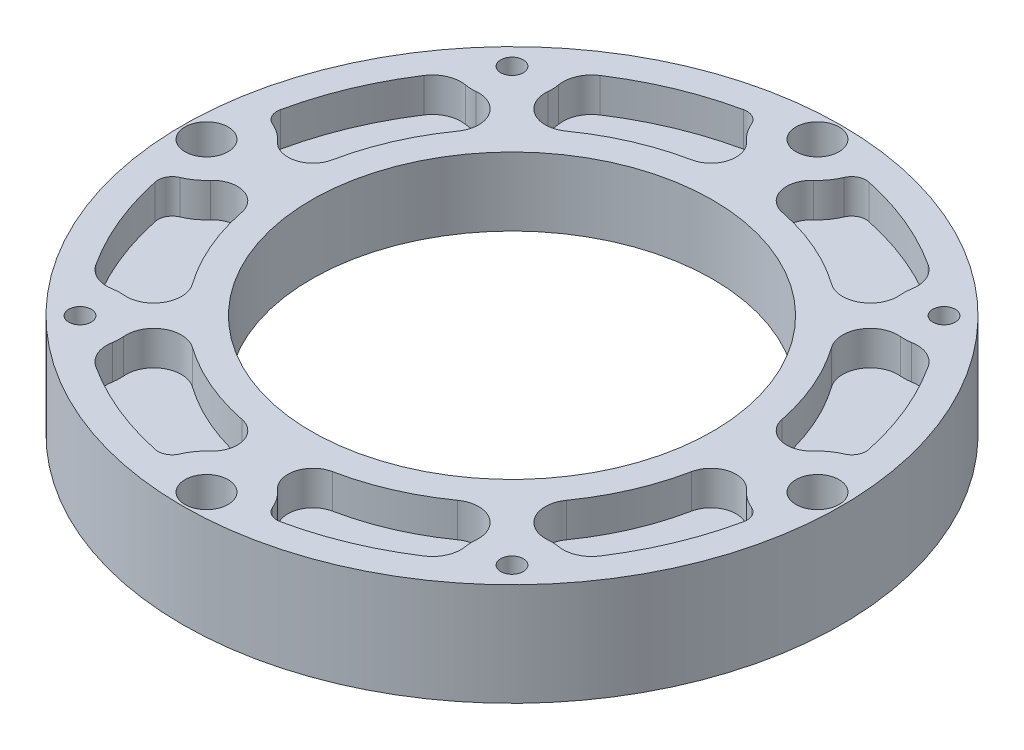
SolidWorks part; units mm, degrees
ref_plane "Front Plane" through (0, 0, 0) normal (0, 0, 1) x (1, 0, 0)
ref_plane "Top Plane" through (0, 0, 0) normal (0, 1, 0) x (1, 0, 0)
ref_plane "Right Plane" through (0, 0, 0) normal (1, 0, 0) x (0, 0, -1)
sketch "Sketch1" plane through (0, 0, 0) normal (0, 1, 0) x (1, 0, 0)
  line L0 (0, 0) -> (42.5, 0) construction
  circle A0 centre (0, 0) radius 45.85
  circle A1 centre (0, 0) radius 27.9
  circle A2 centre (42.5, 0) radius 1.5635
  circle A3 centre (30.052, -30.052) radius 1.5635
  circle A4 centre (0, -42.5) radius 1.5635
  circle A5 centre (0, 0) radius 40.5
  circle A6 centre (-30.052, -30.052) radius 1.5635
  circle A7 centre (-42.5, 0) radius 1.5635
  circle A8 centre (-30.052, 30.052) radius 1.5635
  circle A9 centre (0, 42.5) radius 1.5635
  circle A10 centre (30.052, 30.052) radius 1.5635
  point P13 (0, 0)
  dimension "D1" = 91.7
  dimension "D2" = 55.8
  dimension "D4" = 3.127
  dimension "D6" = 81
  dimension "D3" = 42.5
  dimension "D5" = 8
extrude "Boss-Extrude1" add sketch "Sketch1" against normal blind 4.7625 contours A0 A5 A2 A4 A3 region at (-44.5532, 0, 0)
extrude "Boss-Extrude2" add sketch "Sketch1<4>" along normal blind 4.7625 contours A1 A5 | A0 A5 A2 A4 A3 region at (-44.5532, 0, 0) region at (-39.3545, 0, 0)
sketch "Sketch1<4>" plane through (0, 0, 0) normal (0, 1, 0) x (1, 0, 0) same geometry as "Sketch1"
sketch "Sketch4" plane through (0, 4.7625, 0) normal (0, 1, 0) x (1, 0, 0)
  line L0 (28.4932, -27.352) -> (26.9343, -30.052)
  line L7 (30.052, 33.1697) -> (27.352, 31.6109)
  line L8 (27.352, 31.6109) -> (27.352, 28.4932)
  line L9 (27.352, 28.4932) -> (30.052, 26.9343)
  line L10 (30.052, 26.9343) -> (32.752, 28.4932)
  line L11 (32.752, 28.4932) -> (32.752, 31.6109)
  line L12 (32.752, 31.6109) -> (30.052, 33.1697)
  line L13 (31.6109, -27.352) -> (28.4932, -27.352)
  line L14 (33.1697, -30.052) -> (31.6109, -27.352)
  line L15 (31.6109, -32.752) -> (33.1697, -30.052)
  line L16 (28.4932, -32.752) -> (31.6109, -32.752)
  line L17 (26.9343, -30.052) -> (28.4932, -32.752)
  line L18 (-27.352, -28.4932) -> (-30.052, -26.9343)
  line L19 (-27.352, -31.6109) -> (-27.352, -28.4932)
  line L20 (-30.052, -33.1697) -> (-27.352, -31.6109)
  line L21 (-32.752, -31.6109) -> (-30.052, -33.1697)
  line L22 (-32.752, -28.4932) -> (-32.752, -31.6109)
  line L23 (-30.052, -26.9343) -> (-32.752, -28.4932)
  line L24 (-28.4932, 27.352) -> (-26.9343, 30.052)
  line L25 (-31.6109, 27.352) -> (-28.4932, 27.352)
  line L26 (-33.1697, 30.052) -> (-31.6109, 27.352)
  line L27 (-31.6109, 32.752) -> (-33.1697, 30.052)
  line L28 (-28.4932, 32.752) -> (-31.6109, 32.752)
  line L29 (-26.9343, 30.052) -> (-28.4932, 32.752)
  circle A0 centre (30.052, 30.052) radius 2.7 construction
  point P1 (31.402, 32.3903)
  point P32 (0, 0)
  dimension "D1" = 5.4
  dimension "D2" = 4
extrude "Cut-Extrude2" cut sketch "Sketch4" against normal blind 4.7625
sketch "Sketch3" plane through (0, 4.7625, 0) normal (0, 1, 0) x (1, 0, 0)
  circle A6 centre (0, -42.5) radius 1.5635 construction
  circle A7 centre (42.5, 0) radius 1.5635 construction
  circle A8 centre (0, 42.5) radius 1.5635 construction
  circle A9 centre (-42.5, 0) radius 1.5635 construction
  circle A10 centre (0, 0) radius 27.9 construction
  circle A11 centre (0, 0) radius 45.85 construction
  circle A12 centre (0, -42.5) radius 1.5635
  circle A13 centre (42.5, 0) radius 1.5635
  circle A14 centre (0, 42.5) radius 1.5635
  circle A15 centre (-42.5, 0) radius 1.5635
  circle A16 centre (0, 0) radius 27.9
  circle A17 centre (0, 0) radius 45.85
  circle A18 centre (0, 42.5) radius 3
  circle A19 centre (42.5, 0) radius 3
  circle A20 centre (0, -42.5) radius 3
  circle A21 centre (-42.5, 0) radius 3
  circle A22 centre (-30.052, 30.052) radius 1.565
  circle A23 centre (30.052, 30.052) radius 1.565
  circle A24 centre (30.052, -30.052) radius 1.565
  circle A25 centre (-30.052, -30.052) radius 1.565
  circle M1 centre (0, 0) radius 27.9
  circle M6 centre (0, 0) radius 45.85
  line M21 (-33.1697, 30.052) -> (-31.6109, 32.752)
  line M22 (-31.6109, 32.752) -> (-28.4932, 32.752)
  line M23 (-28.4932, 32.752) -> (-26.9343, 30.052)
  line M24 (-26.9343, 30.052) -> (-28.4932, 27.352)
  line M25 (-28.4932, 27.352) -> (-31.6109, 27.352)
  line M26 (-31.6109, 27.352) -> (-33.1697, 30.052)
  line M27 (-30.052, -33.1697) -> (-32.752, -31.6109)
  line M28 (-32.752, -31.6109) -> (-32.752, -28.4932)
  line M29 (-32.752, -28.4932) -> (-30.052, -26.9343)
  line M30 (-30.052, -26.9343) -> (-27.352, -28.4932)
  line M31 (-27.352, -28.4932) -> (-27.352, -31.6109)
  line M32 (-27.352, -31.6109) -> (-30.052, -33.1697)
  line M33 (33.1697, -30.052) -> (31.6109, -32.752)
  line M34 (31.6109, -32.752) -> (28.4932, -32.752)
  line M35 (28.4932, -32.752) -> (26.9343, -30.052)
  line M36 (26.9343, -30.052) -> (28.4932, -27.352)
  line M37 (28.4932, -27.352) -> (31.6109, -27.352)
  line M38 (31.6109, -27.352) -> (33.1697, -30.052)
  line M39 (30.052, 33.1697) -> (32.752, 31.6109)
  line M40 (32.752, 31.6109) -> (32.752, 28.4932)
  line M41 (32.752, 28.4932) -> (30.052, 26.9343)
  line M42 (30.052, 26.9343) -> (27.352, 28.4932)
  line M43 (27.352, 28.4932) -> (27.352, 31.6109)
  line M44 (27.352, 31.6109) -> (30.052, 33.1697)
  dimension "D1" = 6
  dimension "D2" = 3.13
extrude "Boss-Extrude3" add sketch "Sketch3" along normal blind 4.7625 contours A21 A20 A19 A18 M6 M1 M44 M39 M40 M41 M42 M43 M38 M33 M34 M35 M36 M37 M32 M27 M28 M29 M30 M31 M26 M21 M22 M23 M24 M25 | A22 M21 M26 M25 M24 M23 M22 | A23 M39 M44 M43 M42 M41 M40 | A24 M33 M38 M37 M36 M35 M34 | A25 M27 M32 M31 M30 M29 M28 region at (-45.7203, 4.7625, 0) region at (-32.3189, 4.7625, -31.3608) region at (-31.3608, 4.7625, 32.3189) region at (32.3189, 4.7625, 31.3608) region at (31.3608, 4.7625, -32.3189)
sketch "Sketch5" plane through (0, 9.525, 0) normal (0, 1, 0) x (1, 0, 0)
  line L0 (0, 0) -> (30.052, 30.052) construction
  circle A0 centre (0, 42.5) radius 3 construction
  circle A1 centre (30.052, 30.052) radius 1.565 construction
  circle A2 centre (42.5, 0) radius 3 construction
  circle A3 centre (30.052, -30.052) radius 1.565 construction
  circle A4 centre (0, -42.5) radius 3 construction
  circle A5 centre (-30.052, -30.052) radius 1.565 construction
  circle A6 centre (-42.5, 0) radius 3 construction
  circle A7 centre (-30.052, 30.052) radius 1.565 construction
  circle A8 centre (0, 0) radius 45.85 construction
  circle A9 centre (0, 0) radius 27.9 construction
  circle A10 centre (0, 42.5) radius 3
  circle A11 centre (30.052, 30.052) radius 1.565
  circle A12 centre (42.5, 0) radius 3
  circle A13 centre (30.052, -30.052) radius 1.565
  circle A14 centre (0, -42.5) radius 3
  circle A15 centre (-30.052, -30.052) radius 1.565
  circle A16 centre (-42.5, 0) radius 3
  circle A17 centre (-30.052, 30.052) radius 1.565
  circle A18 centre (0, 0) radius 45.85
  circle A19 centre (0, 0) radius 27.9
  arc A20 (6.31, 31.2697) -> (18.4511, 26.0224) centre (0, 0) cw
  arc A21 (4.6718, 37.2871) -> (6.4423, 39.762) centre (0, 42.5) ccw
  arc A22 (24.5734, 31.0284) -> (24.5119, 29.527) centre (30.052, 30.052) ccw
  arc A23 (24.5119, 29.527) -> (18.4511, 26.0224) centre (20.6784, 29.1636) cw
  arc A24 (4.6718, 37.2871) -> (6.31, 31.2697) centre (7, 34.6892) ccw
  arc A25 (22.8162, 35.0834) -> (24.5734, 31.0284) centre (20.6354, 31.7302) cw
  arc A26 (8.6987, 40.936) -> (6.4423, 39.762) centre (8.283, 38.9797) ccw
  arc A27 (22.8162, 35.0834) -> (8.6987, 40.936) centre (0, 0) ccw
  arc A28 (35.0834, 22.8162) -> (31.0284, 24.5734) centre (31.7302, 20.6354) ccw
  arc A29 (31.0284, 24.5734) -> (29.527, 24.5119) centre (30.052, 30.052) cw
  arc A30 (29.527, 24.5119) -> (26.0224, 18.4511) centre (29.1636, 20.6784) ccw
  arc A31 (31.2697, 6.31) -> (26.0224, 18.4511) centre (0, 0) ccw
  arc A32 (35.0834, 22.8162) -> (40.936, 8.6987) centre (0, 0) cw
  arc A33 (40.936, 8.6987) -> (39.762, 6.4423) centre (38.9797, 8.283) cw
  arc A34 (37.2871, 4.6718) -> (39.762, 6.4423) centre (42.5, 0) cw
  arc A35 (37.2871, 4.6718) -> (31.2697, 6.31) centre (34.6892, 7) cw
  arc A36 (37.2871, -4.6718) -> (31.2697, -6.31) centre (34.6892, -7) ccw
  arc A37 (31.2697, -6.31) -> (26.0224, -18.4511) centre (0, 0) cw
  arc A38 (29.527, -24.5119) -> (26.0224, -18.4511) centre (29.1636, -20.6784) cw
  arc A39 (31.0284, -24.5734) -> (29.527, -24.5119) centre (30.052, -30.052) ccw
  arc A40 (35.0834, -22.8162) -> (31.0284, -24.5734) centre (31.7302, -20.6354) cw
  arc A41 (35.0834, -22.8162) -> (40.936, -8.6987) centre (0, 0) ccw
  arc A42 (40.936, -8.6987) -> (39.762, -6.4423) centre (38.9797, -8.283) ccw
  arc A43 (37.2871, -4.6718) -> (39.762, -6.4423) centre (42.5, 0) ccw
  arc A44 (24.5119, -29.527) -> (18.4511, -26.0224) centre (20.6784, -29.1636) ccw
  arc A45 (24.5734, -31.0284) -> (24.5119, -29.527) centre (30.052, -30.052) cw
  arc A46 (22.8162, -35.0834) -> (24.5734, -31.0284) centre (20.6354, -31.7302) ccw
  arc A47 (22.8162, -35.0834) -> (8.6987, -40.936) centre (0, 0) cw
  arc A48 (6.31, -31.2697) -> (18.4511, -26.0224) centre (0, 0) ccw
  arc A49 (4.6718, -37.2871) -> (6.31, -31.2697) centre (7, -34.6892) cw
  arc A50 (4.6718, -37.2871) -> (6.4423, -39.762) centre (0, -42.5) cw
  arc A51 (8.6987, -40.936) -> (6.4423, -39.762) centre (8.283, -38.9797) cw
  arc A52 (-4.6718, -37.2871) -> (-6.31, -31.2697) centre (-7, -34.6892) ccw
  arc A53 (-6.31, -31.2697) -> (-18.4511, -26.0224) centre (0, 0) cw
  arc A54 (-24.5119, -29.527) -> (-18.4511, -26.0224) centre (-20.6784, -29.1636) cw
  arc A55 (-24.5734, -31.0284) -> (-24.5119, -29.527) centre (-30.052, -30.052) ccw
  arc A56 (-22.8162, -35.0834) -> (-24.5734, -31.0284) centre (-20.6354, -31.7302) cw
  arc A57 (-22.8162, -35.0834) -> (-8.6987, -40.936) centre (0, 0) ccw
  arc A58 (-8.6987, -40.936) -> (-6.4423, -39.762) centre (-8.283, -38.9797) ccw
  arc A59 (-4.6718, -37.2871) -> (-6.4423, -39.762) centre (0, -42.5) ccw
  arc A60 (-29.527, -24.5119) -> (-26.0224, -18.4511) centre (-29.1636, -20.6784) ccw
  arc A61 (-31.0284, -24.5734) -> (-29.527, -24.5119) centre (-30.052, -30.052) cw
  arc A62 (-35.0834, -22.8162) -> (-31.0284, -24.5734) centre (-31.7302, -20.6354) ccw
  arc A63 (-35.0834, -22.8162) -> (-40.936, -8.6987) centre (0, 0) cw
  arc A64 (-31.2697, -6.31) -> (-26.0224, -18.4511) centre (0, 0) ccw
  arc A65 (-37.2871, -4.6718) -> (-31.2697, -6.31) centre (-34.6892, -7) cw
  arc A66 (-37.2871, -4.6718) -> (-39.762, -6.4423) centre (-42.5, 0) cw
  arc A67 (-40.936, -8.6987) -> (-39.762, -6.4423) centre (-38.9797, -8.283) cw
  arc A68 (-37.2871, 4.6718) -> (-31.2697, 6.31) centre (-34.6892, 7) ccw
  arc A69 (-31.2697, 6.31) -> (-26.0224, 18.4511) centre (0, 0) cw
  arc A70 (-29.527, 24.5119) -> (-26.0224, 18.4511) centre (-29.1636, 20.6784) cw
  arc A71 (-31.0284, 24.5734) -> (-29.527, 24.5119) centre (-30.052, 30.052) ccw
  arc A72 (-35.0834, 22.8162) -> (-31.0284, 24.5734) centre (-31.7302, 20.6354) cw
  arc A73 (-35.0834, 22.8162) -> (-40.936, 8.6987) centre (0, 0) ccw
  arc A74 (-40.936, 8.6987) -> (-39.762, 6.4423) centre (-38.9797, 8.283) ccw
  arc A75 (-37.2871, 4.6718) -> (-39.762, 6.4423) centre (-42.5, 0) ccw
  arc A76 (-24.5119, 29.527) -> (-18.4511, 26.0224) centre (-20.6784, 29.1636) ccw
  arc A77 (-24.5734, 31.0284) -> (-24.5119, 29.527) centre (-30.052, 30.052) cw
  arc A78 (-22.8162, 35.0834) -> (-24.5734, 31.0284) centre (-20.6354, 31.7302) ccw
  arc A79 (-22.8162, 35.0834) -> (-8.6987, 40.936) centre (0, 0) cw
  arc A80 (-6.31, 31.2697) -> (-18.4511, 26.0224) centre (0, 0) ccw
  arc A81 (-4.6718, 37.2871) -> (-6.31, 31.2697) centre (-7, 34.6892) cw
  arc A82 (-4.6718, 37.2871) -> (-6.4423, 39.762) centre (0, 42.5) cw
  arc A83 (-8.6987, 40.936) -> (-6.4423, 39.762) centre (-8.283, 38.9797) cw
  point P137 (0, 0)
  dimension "D1" = 4
  dimension "D2" = 4
  dimension "D3" = 4
  dimension "D4" = 4
  dimension "D5" = 12
  dimension "D8" = 2
  dimension "D9" = 4
  dimension "D7" = 14
  dimension "D6" = 4
extrude "Cut-Extrude3" cut sketch "Sketch5" against normal blind 4.7625 contours A75 A68 A69 A70 A71 A72 A73 A74 | A83 A79 A78 A77 A76 A80 A81 A82 | A25 A27 A26 A21 A24 A20 A23 A22 | A35 A34 A33 A32 A28 A29 A30 A31 | A43 A36 A37 A38 A39 A40 A41 A42 | A51 A47 A46 A45 A44 A48 A49 A50 | A59 A52 A53 A54 A55 A56 A57 A58 | A67 A63 A62 A61 A60 A64 A65 A66 region at (14.5651, 9.525, -33.3777) region at (33.3777, 9.525, -14.5651) region at (33.3777, 9.525, 14.5651) region at (14.5651, 9.525, 33.3777) region at (-14.5651, 9.525, 33.3777) region at (-33.3777, 9.525, 14.5651) region at (-33.3777, 9.525, -14.5651) region at (-14.5651, 9.525, -33.3777)
equation "\"bearing_21_OD\"= 21mm"
equation "\"pin_cirlce_diameter\"= 75mm"
equation "\"pin_diam\"= 6mm"
equation "\"gear_thickness\"= 4mm"
equation "\"ball_bearing_diam\"= 3.214mm"
equation "\"bearing_21_outer_clearance\"= 0.127mm'change this"
equation "\"bearing_15_OD\"= 15mm"
equation "\"bearing_15_outer_clearance\"= 0mm'change this"
equation "\"thrust_bearing_thickness\"= 5mm'measure this irl and change"
equation "\"D1@Boss-Extrude1\"=\"sheetThickness\""
equation "\"largeBearOD\"= 21mm"
equation "\"largeBearID\" = 15mm"
equation "\"largeBearOTight\"= 0.34375mm'calibrate - hold onto gears"
equation "\"largeBearITight\"= 0mm'calibrate - hold onto eccentric nut"
equation "\"largeBearFlangeDiam\" = 22.5mm"
equation "\"largeBearFlangeWidth\" = 0.8mm"
equation "\"smallBearOD\"= 14.8mm"
equation "\"smallBearOTight\"= 0mm'calibrate - hold onto bottom of gearbox"
equation "\"smallBearOLoose\"= 0mm'calibrate - able to take off topHat"
equation "\"smallBearID\" = 10mm"
equation "\"smallBearITight\" = 0mm'hold onto "
equation "\"pinCircleDiam\"= 75mm"
equation "\"pinDiam\"= 6mm"
equation "\"sheetThickness\"= 0.1875in"
equation "\"ballBearDiam\"= 3.5mm"
equation "\"thrustBearingThickness\"= 5mm'measure this irl and change"
equation "\"thrustBearingID\"= 0mm'measure this irl and change"
equation "\"thrustBearingOD\"= 0mm'measure this irl and change"
equation "\"eccentricity\" = 1mm"
equation "\"D1@Boss-Extrude2\"=\"sheetThickness\""
equation "\"D1@Boss-Extrude3\"=\"sheetThickness\""
equation "\"D1@Cut-Extrude2\"=\"sheetThickness\""
equation "\"D1@Cut-Extrude3\"=\"sheetThickness\""
